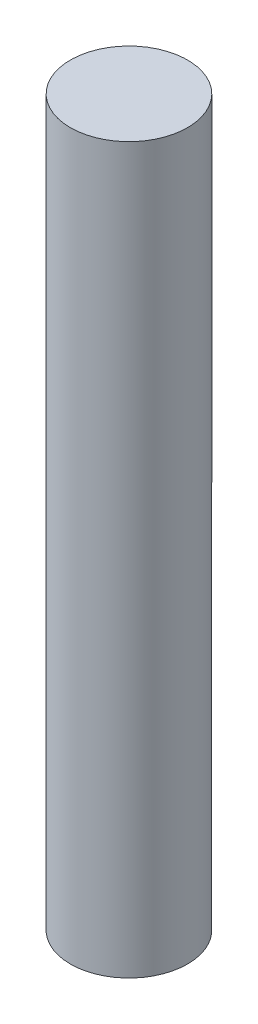
SolidWorks part; units mm, degrees
ref_plane "Front Plane" through (0, 0, 0) normal (0, 0, 1) x (1, 0, 0)
ref_plane "Top Plane" through (0, 0, 0) normal (0, 1, 0) x (1, 0, 0)
ref_plane "Right Plane" through (0, 0, 0) normal (1, 0, 0) x (0, 0, -1)
sketch "Sketch1" plane through (0, 0, 0) normal (0, 1, 0) x (1, 0, 0)
  circle A0 centre (0, 0) radius 3
  dimension "D1" = 6
extrude "Boss-Extrude1" add sketch "Sketch1" along normal blind 80
sketch "Sketch2" plane through (0, 80, 0) normal (0, 1, 0) x (1, 0, 0)
  circle A0 centre (0, 0) radius 6.35
  dimension "D1" = 12.7
extrude "Boss-Extrude2" add sketch "Sketch2" against normal blind 600
sketch "Sketch3" plane through (0, 0, 0) normal (1, 0, 0) x (0, 0, -1)
  line L0 (6.35, -520) -> (6.35, 80) construction
  line L1 (-6.35, -520) -> (6.35, -520)
  line L2 (-6.35, -520) -> (-6.35, 1.5)
  line L3 (-6.35, 1.5) -> (6.35, 1.5)
  line L4 (6.35, -520) -> (6.35, 1.5)
  dimension "D1" = 521.5
extrude "Cut-Extrude1" cut sketch "Sketch3" against normal blind 7 and the other way blind 7
sketch "Sketch4" [suppressed] plane through (0, 80, 0) normal (0, 1, 0) x (1, 0, 0)
  circle A0 centre (0, 0) radius 3
extrude "Boss-Extrude3" [suppressed] add sketch "Sketch4" along normal blind 120
sketch "Sketch5" [suppressed] plane through (0, 200, 0) normal (0, 1, 0) x (1, 0, 0)
  circle A0 centre (0, 0) radius 3
extrude "Cut-Extrude2" [suppressed] cut sketch "Sketch5" against normal blind 100
